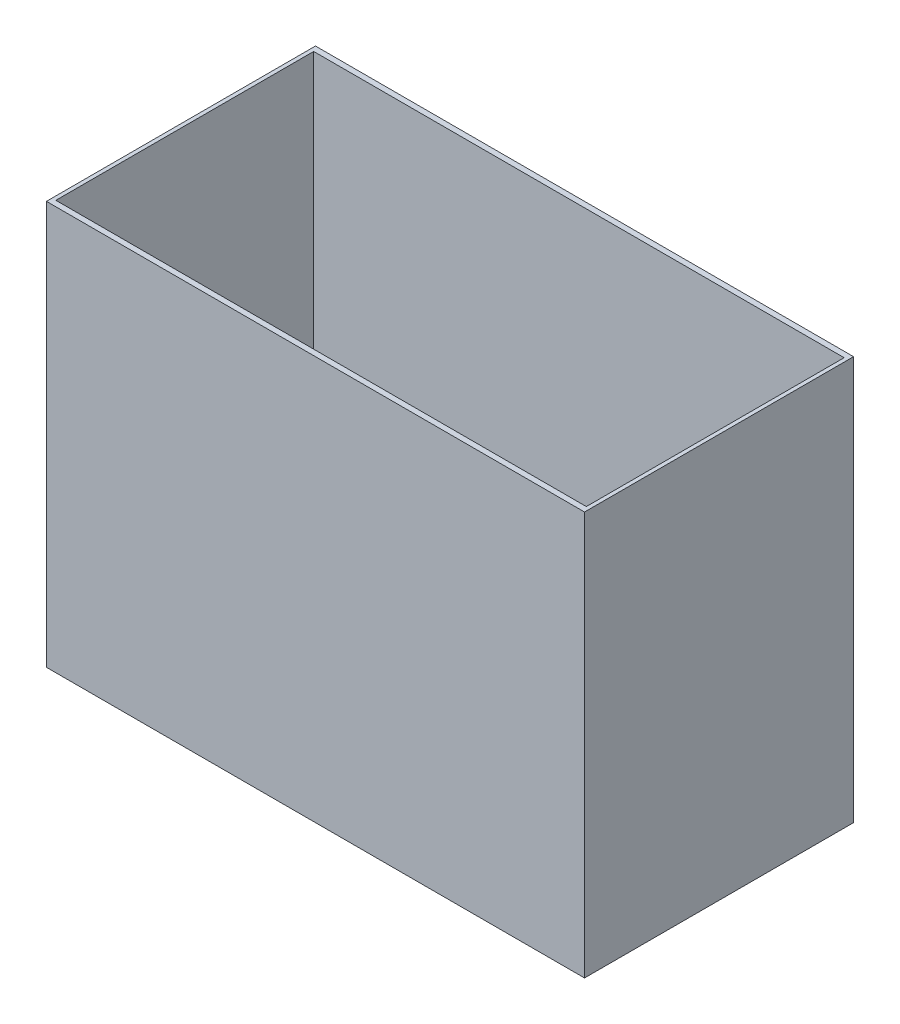
SolidWorks part; units mm, degrees
ref_plane "Front Plane" through (0, 0, 0) normal (0, 0, 1) x (1, 0, 0)
ref_plane "Top Plane" through (0, 0, 0) normal (0, 1, 0) x (1, 0, 0)
ref_plane "Right Plane" through (0, 0, 0) normal (1, 0, 0) x (0, 0, -1)
other "Bounding Box"
ref_plane "Default Plane" through (-292.1, 0, -139.7) normal (0, 1, 0) x (1, 0, 0)
sketch "Sketch1" plane through (0, 0, 0) normal (0, 1, 0) x (1, 0, 0)
  line L0 (-292.1, 0) -> (292.1, 0) construction
  line L1 (-292.1, 139.7) -> (292.1, 139.7)
  line L2 (-292.1, 139.7) -> (-292.1, -139.7)
  line L3 (-292.1, -139.7) -> (292.1, -139.7)
  line L4 (292.1, 139.7) -> (292.1, -139.7)
  line L5 (0, 139.7) -> (0, -139.7) construction
  point P8 (0, 0)
  dimension "D1" = 584.2
  dimension "D2" = 279.4
extrude "Boss-Extrude1" add sketch "Sketch1" along normal blind 6.35
sketch "Sketch2" plane through (0, 6.35, 0) normal (0, 1, 0) x (1, 0, 0)
  line L0 (-245.9259, -63.5) -> (-55.3589, -63.5) construction
  line L1 (-241.3, -120.6497) -> (-152.4, -120.6497)
  line L2 (-241.3, -120.6497) -> (-241.3, -101.5997)
  line L3 (-241.3, -101.5997) -> (-152.4, -101.5997)
  line L4 (-152.4, -120.6497) -> (-152.4, -101.5997)
  line L5 (-241.3, -120.6497) -> (-152.4, -101.5997) construction
  line L6 (-241.3, -101.5997) -> (-152.4, -120.6497) construction
  line L7 (-292.1, 139.7) -> (-292.1, -139.7) construction
  line L8 (-292.1, 0) -> (292.1, 0) construction
  line L9 (292.1, -139.7) -> (292.1, 139.7) construction
  line L10 (0, 0) -> (0, 121.6784) construction
  line L11 (241.3, -101.5997) -> (152.4, -120.6497) construction
  line L12 (241.3, -120.6497) -> (152.4, -101.5997) construction
  line L13 (152.4, -120.6497) -> (152.4, -101.5997)
  line L14 (241.3, -101.5997) -> (152.4, -101.5997)
  line L15 (241.3, -120.6497) -> (241.3, -101.5997)
  line L16 (241.3, -120.6497) -> (152.4, -120.6497)
  point P0 (-196.85, -111.1247)
  point P17 (196.85, -111.1247)
  dimension "D1" = 19.05
  dimension "D2" = 88.9
  dimension "D3" = 38.0997
  dimension "D4" = 50.8
  dimension "D5" = 63.5
extrude "Boss-Extrude2" [suppressed] add sketch "Sketch2" along normal blind 304.8 separate body contours L2 L1 L4 L3
pattern_linear "LPattern1" [suppressed] count 2 spacing 304.8 of bodies 101
pattern_linear "LPattern2" [suppressed] count 2 spacing 215.9 of bodies 101
sketch "Sketch3" plane through (0, 0, 0) normal (0, 1, 0) x (1, 0, 0)
  line L1 (-304.8, -152.4) -> (304.8, -152.4)
  line L2 (-304.8, -152.4) -> (-304.8, 152.4)
  line L3 (-304.8, 152.4) -> (304.8, 152.4)
  line L4 (304.8, -152.4) -> (304.8, 152.4)
  line L5 (-304.8, -152.4) -> (304.8, 152.4) construction
  line L6 (-304.8, 152.4) -> (304.8, -152.4) construction
  line L7 (-300.482, -146.05) -> (300.482, -146.05)
  line L8 (-300.482, -146.05) -> (-300.482, 146.05)
  line L9 (-300.482, 146.05) -> (300.482, 146.05)
  line L10 (300.482, -146.05) -> (300.482, 146.05)
  line L11 (-300.482, -146.05) -> (300.482, 146.05) construction
  line L12 (-300.482, 146.05) -> (300.482, -146.05) construction
  point P0 (0, 0)
  point P6 (0, 0)
  dimension "D1" = 609.6
  dimension "D2" = 304.8
  dimension "D3" = 292.1
  dimension "D4" = 600.964
extrude "Boss-Extrude3" add sketch "Sketch3" along normal blind 457.2 separate body
sketch "Sketch4" plane through (0, 6.35, 0) normal (0, 1, 0) x (1, 0, 0)
  circle A0 centre (273.05, 120.65) radius 2.7781
  circle A1 centre (273.05, 120.65) radius 4 construction
  circle A2 centre (273.05, 120.65) radius 4 construction
  dimension "D1" = 5.5562
extrude "Cut-Extrude1" cut sketch "Sketch4" against normal through all
sketch "Sketch6" plane through (0, 0, 0) normal (0, -1, 0) x (1, 0, 0)
  circle A0 centre (273.05, -120.65) radius 6.35
  circle A1 centre (273.05, -120.65) radius 2.7781 construction
  dimension "D1" = 12.7
extrude "Cut-Extrude2" cut sketch "Sketch6" against normal blind 2.54
mirror "Mirror1" about plane through (0, 0, 0) normal (0, 0, 1) of "Cut-Extrude2", "Cut-Extrude1"
sketch "Sketch7" plane through (0, 6.35, 0) normal (0, 1, 0) x (1, 0, 0)
  line L0 (292.1, 0) -> (49.4912, 0) construction
  line L1 (292.1, -139.7) -> (292.1, 139.7) construction
  circle A0 centre (190.5, 0) radius 4 construction
  circle A1 centre (190.5, 0) radius 2.7781
  dimension "D1" = 8
  dimension "D2" = 5.5562
  dimension "D3" = 101.6
extrude "Cut-Extrude3" cut sketch "Sketch7" against normal through all
sketch "Sketch8" plane through (0, 6.35, 0) normal (0, 1, 0) x (1, 0, 0)
  circle A0 centre (94.9, -12.8415) radius 1.9844 construction
  circle A1 centre (146.1, -12.8415) radius 1.9844 construction
  circle A2 centre (146.1, 12.8415) radius 1.9844 construction
  circle A3 centre (94.9, 12.8415) radius 1.9844 construction
  circle A4 centre (94.9, -12.8415) radius 1.9844
  circle A5 centre (146.1, -12.8415) radius 1.9844
  circle A6 centre (146.1, 12.8415) radius 1.9844
  circle A7 centre (94.9, 12.8415) radius 1.9844
extrude "Cut-Extrude4" cut sketch "Sketch8" against normal through all
sketch "Sketch9" plane through (0, 0, 0) normal (0, -1, 0) x (1, 0, 0)
  circle A1 centre (190.5, 0) radius 6.35
  circle A2 centre (146.1, 12.8415) radius 6.35
  circle A3 centre (94.9, 12.8415) radius 6.35
  circle A4 centre (94.9, -12.8415) radius 6.35
  circle A5 centre (146.1, -12.8415) radius 6.35
  circle A6 centre (273.05, 120.65) radius 6.35 construction
extrude "Cut-Extrude5" cut sketch "Sketch9" against normal blind 3.175
sketch "Sketch11" plane through (0, 0, 0) normal (0, -1, 0) x (1, 0, 0)
  line L0 (-292.1, 139.7) -> (292.1, 139.7) construction
  line L1 (215.9, 139.7) -> (165.1, 139.7)
  line L2 (215.9, 139.7) -> (215.9, 136.525)
  line L3 (215.9, 136.525) -> (165.1, 136.525)
  line L4 (165.1, 139.7) -> (165.1, 136.525)
  line L5 (292.1, 139.7) -> (292.1, -139.7) construction
  dimension "D1" = 3.175
  dimension "D2" = 50.8
  dimension "D3" = 76.2
extrude "Cut-Extrude6" cut sketch "Sketch11" against normal through all
mirror "Mirror2" about plane through (0, 0, 0) normal (0, 0, 1) of "Cut-Extrude6"
